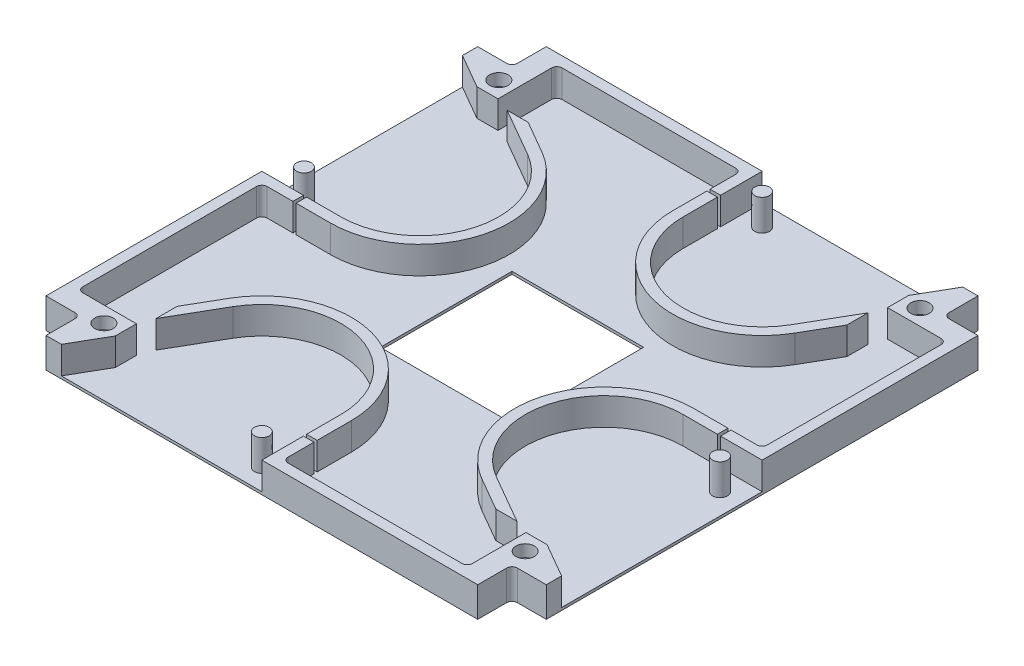
SolidWorks part; units mm, degrees
note: '?' marks a value the reader was unsure of.
material "7075-T6 (SN)"
ref_plane "Front Plane" through (0, 0, 0) normal (0, 0, 1) x (1, 0, 0)
ref_plane "Top Plane" through (0, 0, 0) normal (0, 1, 0) x (1, 0, 0)
ref_plane "Right Plane" through (0, 0, 0) normal (1, 0, 0) x (0, 0, -1)
sketch "Sketch1" plane through (0, 0, 0) normal (0, 1, 0) x (1, 0, 0)
  line L0 (0, 0) -> (0, 6.51)
  line L21 (0, 6.51) -> (82, 6.51)
  line L22 (82, 6.51) -> (82, 0)
  line L23 (82, 0) -> (88.51, 0)
  line L24 (88.51, 0) -> (88.51, -82)
  line L25 (88.51, -82) -> (82, -82)
  line L26 (82, -82) -> (82, -88.51)
  line L27 (82, -88.51) -> (0, -88.51)
  line L28 (0, -88.51) -> (0, -82)
  line L29 (0, -82) -> (-6.51, -82)
  line L30 (-6.51, -82) -> (-6.51, 0)
  line L31 (-6.51, 0) -> (0, 0)
  dimension "D1" = 82
  dimension "D2" = 6.51
extrude "Boss-Extrude1" add sketch "Sketch1" along normal blind 0.5
sketch "Sketch2" plane through (0, 0.5, 0) normal (0, 1, 0) x (1, 0, 0)
  line L0 (-6.51, 0) -> (-6.51, -82) construction
  line L1 (0, 6.51) -> (41, 6.51)
  line L2 (0, 6.51) -> (0, 4.51)
  line L3 (0, 4.51) -> (41, 4.51)
  line L4 (41, 6.51) -> (41, 4.51)
  line L5 (88.51, 0) -> (86.51, 0)
  line L6 (88.51, 0) -> (88.51, -41)
  line L7 (88.51, -41) -> (86.51, -41)
  line L8 (86.51, 0) -> (86.51, -41)
  line L9 (82, -88.51) -> (41, -88.51)
  line L10 (82, -88.51) -> (82, -86.51)
  line L11 (82, -86.51) -> (41, -86.51)
  line L12 (41, -88.51) -> (41, -86.51)
  line L13 (-6.51, -82) -> (-4.51, -82)
  line L14 (-6.51, -82) -> (-6.51, -41)
  line L15 (-6.51, -41) -> (-4.51, -41)
  line L16 (-4.51, -82) -> (-4.51, -41)
  line L17 (-6.51, -82) -> (0, -82) construction
  line L18 (41, -8.49) -> (41, 24.5303) construction
  line L19 (56, 6.51) -> (0, 6.51) construction
  line L20 (82, 6.51) -> (0, 6.51) construction
  line L21 (79.094, 6.51) -> (75.3355, 0)
  line L22 (79.094, 6.51) -> (82, 6.51)
  line L23 (82, 6.51) -> (82, 0)
  line L24 (82, 0) -> (86.51, 0)
  line L25 (41, 4.51) -> (41, -8.49)
  line L26 (86.51, -4) -> (75.3355, -4)
  line L27 (39, 4.51) -> (39, -8.49)
  line L28 (72.9929, -8) -> (73.0261, -8)
  line L29 (74.3355, -10.7321) -> (70.7224, -16.99)
  line L31 (75.3355, -4) -> (75.3355, 0)
  line L32 (74.3355, -6.7321) -> (74.3355, -10.7321)
  line L33 (74.3355, -6.7321) -> (68.9904, -15.99)
  circle A0 centre (56, -8.49) radius 15
  circle A1 centre (56, -8.49) radius 17 construction
  arc A2 (70.7224, -16.99) -> (39, -8.49) centre (56, -8.49) cw
  dimension "D3" = 30
  dimension "D6" = 34
  dimension "D1" = 41
  dimension "D2" = 2
  dimension "D7" = 4
  dimension "D8" = 4
  dimension "D5" = 0
  dimension "D9" = 1
  dimension "D4" = 30
  dimension "D10" = 6.6645
  dimension "D11" = 30
  dimension "D12" = 4
extrude "Boss-Extrude2" add sketch "Sketch2" along normal blind 5.2
sketch "Sketch3" [suppressed] plane through (0, 0.5, 0) normal (0, 1, 0) x (1, 0, 0)
  line L0 (35.5217, -6.4679) -> (39.51, -26.4679)
  line L1 (39.51, -26.4679) -> (39.51, -29.4679)
  line L2 (39.51, -29.4679) -> (79.51, -29.4679)
  line L3 (79.51, -29.4679) -> (79.51, -26.4679)
  line L4 (79.51, -26.4679) -> (83.4983, -6.4679)
  line L6 (35.5217, -6.4679) -> (39.5217, -6.4679)
  line L7 (83.4983, -6.4679) -> (79.4983, -6.4679)
  line L9 (89.51, -41) -> (89.51, 0) construction
  arc A0 (79.4983, -6.4679) -> (39.5217, -6.4679) centre (59.51, -5.7836) cw
  circle A1 centre (58.485, 0) radius 15 construction
  dimension "D3" = 20
  dimension "D7" = 30
  dimension "D1" = 3
  dimension "D2" = 4
  dimension "D4" = 20
  dimension "D5" = 40
  dimension "D6" = 10
extrude "Boss-Extrude3" [suppressed] add sketch "Sketch3" along normal blind 6
ref_plane "Plane1" through (41, 0, 41) normal (0.7071, 0, 0.7071) x (0.7071, 0, -0.7071)
ref_plane "Plane2" through (0, 0, 0) normal (0.7071, 0, -0.7071) x (-0.7071, 0, -0.7071)
ref_axis "Axis1" through (41, -0.325, 41) along (0, 1, 0)?
pattern_circular "CirPattern1" count 4 every 90 about axis through (41, 0, 41) along (0, 1, 0) of "Boss-Extrude2"
sketch "Sketch4" plane through (0, 0, 0) normal (0, -1, 0) x (1, 0, 0)
  line L0 (78, -6.51) -> (78, -0.51) construction
  line L1 (82, -6.51) -> (0, -6.51) construction
  line L2 (82, 0) -> (82, -6.51) construction
  line L3 (88.51, 78) -> (82.51, 78) construction
  line L4 (88.51, 82) -> (88.51, 0) construction
  line L5 (4, 88.51) -> (4, 82.51) construction
  line L6 (0, 88.51) -> (82, 88.51) construction
  line L7 (-6.51, 4) -> (-0.51, 4) construction
  line L8 (-6.51, 0) -> (-6.51, 82) construction
  line L10 (82, 82) -> (88.51, 82) construction
  line L11 (0, 82) -> (0, 88.51) construction
  line L12 (0, 0) -> (-6.51, 0) construction
  point P7 (78, -0.51)
  dimension "D1" = 6
  dimension "D2" = 4
  dimension "D3" = 4
  dimension "D4" = 4
  dimension "D5" = 4
  dimension "D6" = 6
  dimension "D7" = 6
  dimension "D8" = 6
sketch "Sketch8" plane through (0, 0.5, 0) normal (0, 1, 0) x (1, 0, 0)
  line L0 (2.906, -88.51) -> (41, -88.51) construction
  line L1 (41, -88.51) -> (41, -73.51) construction
  circle A0 centre (37, -84.51) radius 1.4
  dimension "D1" = 2.8
  dimension "D2" = 4
  dimension "D3" = 4
extrude "Boss-Extrude4" add sketch "Sketch8" along normal blind 5.9
pattern_circular "CirPattern2" count 4 every 90 about axis through (41, 0, 41) along (0, 1, 0) of "Boss-Extrude4"
fillet "Fillet1" radius 1 8 edges at (-4.51, 3.1, 78) (-4.51, 3.1, 43) (4, 3.1, -4.51) (39, 3.1, -4.51) (86.51, 3.1, 4) (86.51, 3.1, 39) (78, 3.1, 86.51) (43, 3.1, 86.51)
sketch "Sketch11" plane through (0, 0.5, 0) normal (0, 1, 0) x (1, 0, 0)
  line L0 (53.5, -53.5) -> (53.5, -28.5)
  line L1 (53.5, -28.5) -> (28.5, -28.5)
  line L2 (28.5, -28.5) -> (28.5, -53.5)
  line L3 (28.5, -53.5) -> (53.5, -53.5)
  line L5 (79.094, 6.51) -> (41, 6.51) construction
  line L6 (-6.51, -2.906) -> (-6.51, -41) construction
  dimension "D1" = 25
  dimension "D2" = 25
  dimension "D3" = 35.01
  dimension "D4" = 35.01
extrude "Cut-Extrude2" cut sketch "Sketch11" against normal through all
sketch "Sketch14" plane through (0, 6.4, 0) normal (0, 1, 0) x (1, 0, 0)
  point P0 (37, -84.51)
sketch "Sketch15" plane through (0, 5.7, 0) normal (0, 1, 0) x (1, 0, 0)
  line L0 (82, -82) -> (88.51, -82) construction
  line L2 (78, -85.51) -> (78, -75.3355) construction
  circle A0 centre (81, -78.5) radius 0.9
  circle A1 centre (78.5, -1) radius 0.9
  circle A2 centre (1, -3.5) radius 0.9
  circle A3 centre (3.5, -81) radius 0.9
  point P0 (1, -3.5)
  point P1 (1, -3.5)
  point P2 (3.5, -81)
  point P3 (81, -78.5)
  point P4 (78.5, -1)
  point P5 (3.5, -81)
  dimension "D3" = 1.8
  dimension "D4" = 1.8
  dimension "D5" = 1.8
  dimension "D6" = 1.8
  dimension "D1" = 3.5
  dimension "D2" = 3
extrude "Cut-Extrude3" cut sketch "Sketch15" against normal through all
sketch "Sketch16" plane through (0, 5.7, 0) normal (0, 1, 0) x (1, 0, 0)
  circle A0 centre (78.5, -1) radius 1.75
  circle A1 centre (81, -78.5) radius 1.75
  circle A2 centre (3.5, -81) radius 1.75
  circle A3 centre (1, -3.5) radius 1.75
  dimension "D1" = 3.5
  dimension "D2" = 3.5
  dimension "D3" = 3.5
  dimension "D4" = 3.5
extrude "Cut-Extrude4" cut sketch "Sketch16" against normal blind 2.3
hole_wizard "CBORE for M1.6 SHCS2" positions "3DSketch2" profile "Sketch18" counterbore size "M1.6" standard "ANSI Metric" end condition through all
sketch3d "3DSketch2"
  line L0 (81, 0, 78.5) -> (81, 3.4, 78.5) construction
  line L1 (78.5, 0, 1) -> (78.5, 3.4, 1) construction
  line L2 (1, 0, 3.5) -> (1, 3.4, 3.5) construction
  line L3 (3.5, 0, 81) -> (3.5, 3.4, 81) construction
  point P0 (81, 0, 78.5)
  point P4 (78.5, 0, 1)
  point P8 (1, 0, 3.5)
  point P12 (3.5, 0, 81)
sketch "Sketch18" plane through (81, 0, 78.5) normal (1, 0, 0) x (0, 0, -1)
  line L0 (0, 0) -> (0, 6.4)
  line L1 (0, 6.4) -> (0.9, 6.4)
  line L3 (0.9, 6.4) -> (0.9, 1.6)
  line L4 (0.9, 1.6) -> (1.75, 1.6)
  line L5 (1.75, 1.6) -> (1.75, 0)
  line L7 (1.75, 0) -> (0, 0)
  line L11 (0, -6.35) -> (0, 107.95) construction
  dimension "Thru Hole Dia." = 1.8
  dimension "Thru Hole Depth" = 6.4
  dimension "C'Bore Dia." = 3.5
  dimension "C'Bore Depth" = 1.6
sketch "Sketch20" plane through (0, 5.7, 0) normal (0, 1, 0) x (1, 0, 0)
  line L0 (80.61, -39) -> (80.61, -41)
  line L1 (85.51, -39) -> (73.51, -39) construction
  line L2 (88.51, -41) -> (73.51, -41) construction
  line L3 (80.61, -41) -> (80.01, -41)
  line L4 (80.01, -41) -> (80.01, -39)
  line L5 (80.01, -39) -> (80.61, -39)
  circle A0 centre (84.51, -45) radius 1.4 construction
  dimension "D1" = 3.9
  dimension "D2" = 4.5
sketch "Sketch24" plane through (0, 0.5, 0) normal (0, 1, 0) x (1, 0, 0)
  point P0 (41, -41)
  dimension "D1" = 41
  dimension "D2" = 41
extrude "Cut-Extrude6" cut sketch "Sketch20" against normal up to surface (5.2 mm away) up to face at (41, 0.5, 41)
pattern_circular "CirPattern3" count 4 over 360 about axis through (41, 0, 41) along (0, 1, 0) of "Cut-Extrude6"
fillet "Fillet2" radius 1 4 edges at (0, 2.85, 0) (82, 2.85, 0) (82, 2.85, 82) (0, 2.85, 82)
equation "\"D6@Sketch2\"=\"D3@Sketch2\"+4"
equation "\"D3@Sketch4\"=\"D2@Sketch4\""
equation "\"D4@Sketch4\"=\"D3@Sketch4\""
equation "\"D5@Sketch4\"=\"D4@Sketch4\""
equation "\"D6@Sketch4\"=\"D1@Sketch4\""
equation "\"D7@Sketch4\"=\"D6@Sketch4\""
equation "\"D8@Sketch4\"=\"D7@Sketch4\""
